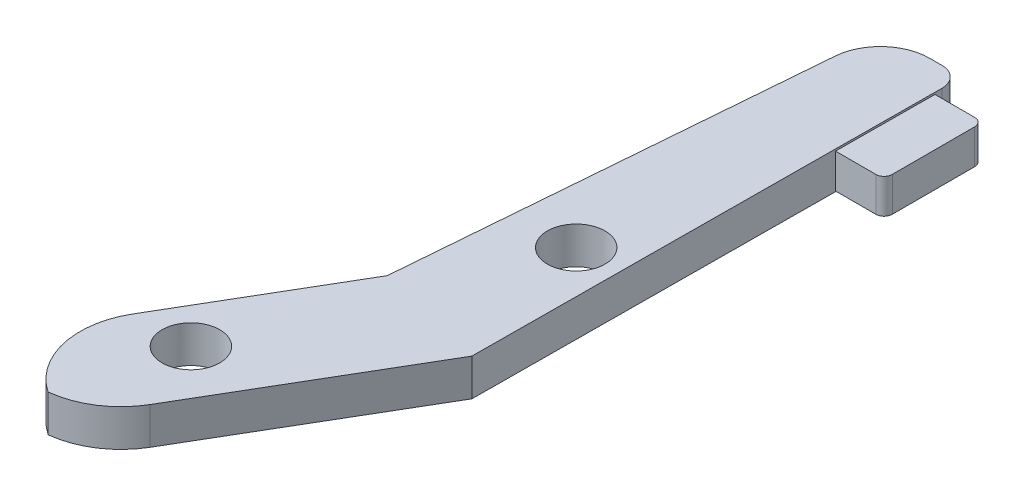
SolidWorks part; units mm, degrees
ref_plane "Front Plane" through (0, 0, 0) normal (0, 0, 1) x (1, 0, 0)
ref_plane "Top Plane" through (0, 0, 0) normal (0, 1, 0) x (1, 0, 0)
ref_plane "Right Plane" through (0, 0, 0) normal (1, 0, 0) x (0, 0, -1)
sketch "Sketch1" plane through (0, 0, 0) normal (0, 1, 0) x (1, 0, 0)
  line L0 (0, 0) -> (9.1036, 15.5282)
  line L1 (9.1036, 15.5282) -> (11.3833, 43.4352)
  line L6 (15.9044, 13.8698) -> (6.8007, -1.6584)
  line L7 (6.8007, -1.6584) -> (0, 0)
  line L9 (15.9044, 13.8698) -> (16.1026, 43.4352)
  line L10 (16.1026, 43.4352) -> (11.3833, 43.4352)
  point P2 (15.5315, 42.5779)
  point P6 (20.3156, 42.4042)
  point P7 (12.0205, 42.7404)
  point P10 (18.5277, 42.6466)
  point P11 (11.1973, 42.8423)
  point P12 (15.1396, 13.5333)
  point P13 (15.4586, 44.8218)
  point P14 (10.5356, 44.7772)
  point P15 (14.1996, 14.9256)
  point P16 (16.4719, 43.8952)
  point P17 (11.4646, 44.4301)
  point P18 (16.1026, 15.5282)
  point P19 (6.8007, -1.6584)
  dimension "D1" = 7
  dimension "D2" = 18
  dimension "D3" = 18
  dimension "D4" = 28
extrude "Boss-Extrude1" add sketch "Sketch1" along normal blind 2.25
fillet "Fillet1" radius 5 2 edges at (6.8007, 1.125, 1.6584) (0, 1.125, 0)
sketch "Sketch2" plane through (0, 2.25, 0) normal (0, 1, 0) x (1, 0, 0)
  line L1 (8.683, 1.5522) -> (15.9044, 13.8698) construction
  circle A0 centre (6.8575, 5.8531) radius 1.75
  circle A2 centre (13.3624, 22.7474) radius 1.75
  point P10 (13.3624, 22.7474)
  dimension "D1" = 3.5
  dimension "D5" = 3.75
ref_plane "Plane1" through (19, 0, 0) normal (1, 0, 0) x (0, 0, -1)
sketch "Sketch4" plane through (19, -1.4847, -8.2019) normal (1, 0, 0) x (0, 0, -1)
  line L1 (33.604, 3.6209) -> (27.604, 3.6209)
  line L2 (33.604, 3.6209) -> (33.604, 1.5209)
  line L3 (33.604, 1.5209) -> (27.604, 1.5209)
  line L4 (27.604, 3.6209) -> (27.604, 1.5209)
  dimension "D1" = 2.1
  dimension "D2" = 6
extrude "Boss-Extrude2" add sketch "Sketch4" against normal up to surface (2.9083 mm away) up to face at (16.0035, 1.125, -28.6525)
extrude "Boss-Extrude3" add sketch "Sketch4<2>" against normal up to surface (2.9083 mm away) up to face at (16.0716, 1.0862, -38.8059)
sketch "Sketch4<2>" plane through (19, -1.4847, -8.2019) normal (1, 0, 0) x (0, 0, -1) same geometry as "Sketch4"
fillet "Fillet2" radius 3 1 edges at (11.3833, 1.125, -43.4352)
fillet "Fillet3" radius 1.2 1 edges at (16.1026, 1.125, -43.4352)
fillet "Fillet4" radius 0.5 2 edges at (19, 1.0862, -35.8059) (19, 1.0862, -41.8059)
extrude "Cut-Extrude1" cut sketch "Sketch2" against normal blind 10
